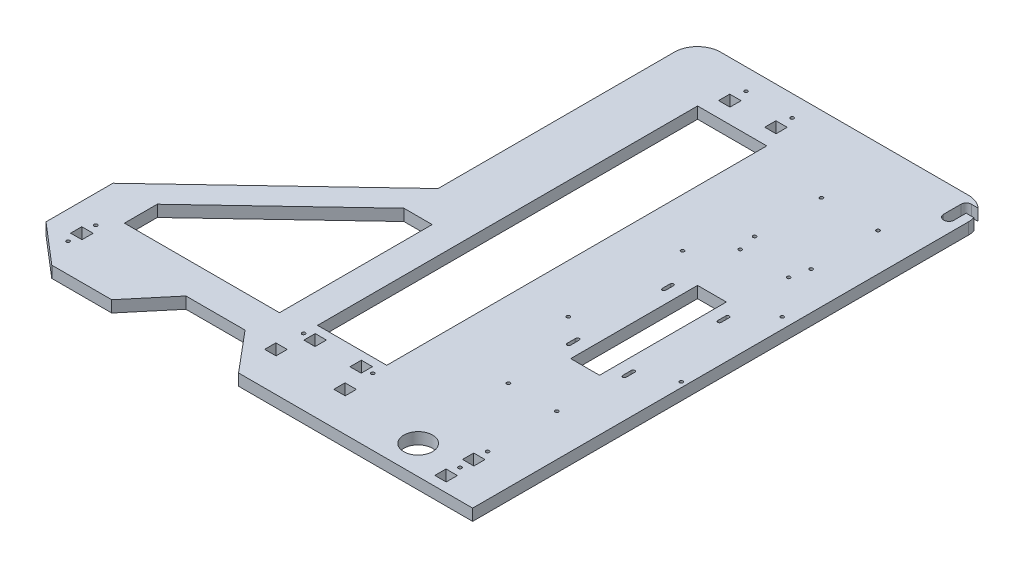
SolidWorks part; units mm, degrees
ref_plane "Front Plane" through (0, 0, 0) normal (0, 0, 1) x (1, 0, 0)
ref_plane "Top Plane" through (0, 0, 0) normal (0, 1, 0) x (1, 0, 0)
ref_plane "Right Plane" through (0, 0, 0) normal (1, 0, 0) x (0, 0, -1)
sketch "Sketch1" plane through (0, 0, 0) normal (0, 1, 0) x (1, 0, 0)
  line L0 (0, 0) -> (-235, 0)
  line L1 (-235, 0) -> (-235, -225)
  line L2 (-235, -225) -> (-380, -362)
  line L3 (-380, -362) -> (-380, -420)
  line L4 (-380, -420) -> (-345, -450)
  line L5 (-345, -450) -> (-293, -450)
  line L6 (-293, -450) -> (-263.6315, -415)
  line L7 (-263.6315, -415) -> (-212.3685, -415)
  line L8 (-212.3685, -415) -> (-183, -450)
  line L9 (-183, -450) -> (0, -450)
  line L10 (0, 0) -> (0, -450)
  line L12 (-293, -450) -> (-183, -450) construction
  dimension "D3" = 235
  dimension "D5" = 58
  dimension "D13" = 190
  dimension "D7" = 35
  dimension "D15" = 52
  dimension "D12" = 30
  dimension "D10" = 35
  dimension "D6" = 380
  dimension "D4" = 450
  dimension "D2" = 50
  dimension "D8" = 50
  dimension "D9" = 110
extrude "Boss-Extrude1" add sketch "Sketch1" along normal blind 10
sketch "Sketch16" plane through (0, 10, 0) normal (0, 1, 0) x (1, 0, 0)
  line L0 (0, -450) -> (20, -450)
  line L1 (20, -450) -> (20, 0)
  line L2 (20, 0) -> (0, 0)
  line L3 (0, 0) -> (0, -450)
  dimension "D1" = 20
  dimension "D2" = 90
extrude "Boss-Extrude2" add sketch "Sketch16" against normal through all
sketch "Sketch2" plane through (0, 10, 0) normal (0, 1, 0) x (1, 0, 0)
  line L0 (-235, -225) -> (-235, -415) construction
  line L1 (-263.6315, -415) -> (-212.3685, -415) construction
  line L2 (-345, -450) -> (-345, -328.931) construction
  line L3 (-235, -225) -> (-380, -362) construction
  line L4 (-345, -358.5097) -> (-235, -254.5787)
  line L5 (-235, -254.5787) -> (-210.5, -254.5787)
  line L6 (-210.5, -254.5787) -> (-210.5, -387)
  line L7 (-210.5, -387) -> (-345, -387)
  line L8 (-345, -387) -> (-345, -358.5097)
  line L9 (0, -450) -> (0, 0) construction
  line L10 (-184.5, -380) -> (-124.5, -380)
  line L11 (-184.5, -380) -> (-184.5, -50.425)
  line L12 (-184.5, -50.425) -> (-124.5, -50.425)
  line L13 (-124.5, -380) -> (-124.5, -50.425)
  line L14 (-124.5, -392.1) -> (-184.5, -392.1) construction
  line L15 (-16, -450) -> (-16, 0) construction
  line L16 (20, 0) -> (-235, 0) construction
  line L17 (-355.9, -440.6571) -> (-355.9, -339.2297) construction
  line L18 (-20.925, -441.85) -> (-11.075, -441.85)
  line L19 (-20.925, -441.85) -> (-20.925, -432.15)
  line L20 (-20.925, -432.15) -> (-11.075, -432.15)
  line L21 (-11.075, -441.85) -> (-11.075, -432.15)
  line L22 (-20.925, -441.85) -> (-11.075, -432.15) construction
  line L23 (-20.925, -432.15) -> (-11.075, -441.85) construction
  line L24 (-20.925, -417.85) -> (-11.075, -417.85)
  line L25 (-20.925, -417.85) -> (-20.925, -408.15)
  line L26 (-20.925, -408.15) -> (-11.075, -408.15)
  line L27 (-11.075, -417.85) -> (-11.075, -408.15)
  line L28 (-20.925, -417.85) -> (-11.075, -408.15) construction
  line L29 (-20.925, -408.15) -> (-11.075, -417.85) construction
  line L30 (-380, -420) -> (-345, -450) construction
  line L32 (-350.975, -408.15) -> (-360.825, -408.15)
  line L33 (-350.975, -408.15) -> (-350.975, -417.85)
  line L34 (-350.975, -417.85) -> (-360.825, -417.85)
  line L35 (-360.825, -408.15) -> (-360.825, -417.85)
  line L36 (-350.975, -408.15) -> (-360.825, -417.85) construction
  line L37 (-350.975, -417.85) -> (-360.825, -408.15) construction
  line L38 (-183, -450) -> (20, -450) construction
  line L39 (-183, -450) -> (20, -450) construction
  line L40 (-173.749, -32.425) -> (-113.749, -32.425) construction
  line L41 (-154.5, -50.425) -> (-154.5, -32.425) construction
  line L42 (-179.425, -27.575) -> (-169.575, -27.575)
  line L43 (-179.425, -27.575) -> (-179.425, -37.275)
  line L44 (-179.425, -37.275) -> (-169.575, -37.275)
  line L45 (-169.575, -27.575) -> (-169.575, -37.275)
  line L46 (-179.425, -27.575) -> (-169.575, -37.275) construction
  line L47 (-179.425, -37.275) -> (-169.575, -27.575) construction
  line L48 (-129.575, -37.275) -> (-139.425, -27.575) construction
  line L49 (-129.575, -27.575) -> (-139.425, -37.275) construction
  line L50 (-139.425, -27.575) -> (-139.425, -37.275)
  line L51 (-129.575, -37.275) -> (-139.425, -37.275)
  line L52 (-129.575, -27.575) -> (-129.575, -37.275)
  line L53 (-129.575, -27.575) -> (-139.425, -27.575)
  line L54 (-174.5, -32.425) -> (-174.5, -18.425) construction
  line L55 (-134.5, -32.425) -> (-134.5, -18.425) construction
  line L56 (-154.5, -380) -> (-154.5, -450) construction
  line L57 (-174.5, -392.1) -> (-134.5, -392.1) construction
  line L58 (-129.65, -397.025) -> (-139.35, -387.175) construction
  line L59 (-179.35, -387.175) -> (-169.65, -387.175)
  line L60 (-179.35, -387.175) -> (-179.35, -397.025)
  line L61 (-179.35, -397.025) -> (-169.65, -397.025)
  line L62 (-169.65, -387.175) -> (-169.65, -397.025)
  line L63 (-179.35, -387.175) -> (-169.65, -397.025) construction
  line L64 (-179.35, -397.025) -> (-169.65, -387.175) construction
  line L65 (-129.65, -387.175) -> (-139.35, -397.025) construction
  line L66 (-139.35, -387.175) -> (-139.35, -397.025)
  line L67 (-129.65, -397.025) -> (-139.35, -397.025)
  line L68 (-129.65, -387.175) -> (-129.65, -397.025)
  line L69 (-129.65, -387.175) -> (-139.35, -387.175)
  line L70 (-119.575, -420.95) -> (-129.425, -411.25) construction
  line L71 (-189.425, -411.25) -> (-179.575, -411.25)
  line L72 (-189.425, -411.25) -> (-189.425, -420.95)
  line L73 (-189.425, -420.95) -> (-179.575, -420.95)
  line L74 (-179.575, -411.25) -> (-179.575, -420.95)
  line L75 (-189.425, -411.25) -> (-179.575, -420.95) construction
  line L76 (-189.425, -420.95) -> (-179.575, -411.25) construction
  line L77 (-119.575, -411.25) -> (-129.425, -420.95) construction
  line L78 (-129.425, -411.25) -> (-129.425, -420.95)
  line L79 (-119.575, -420.95) -> (-129.425, -420.95)
  line L80 (-119.575, -411.25) -> (-119.575, -420.95)
  line L81 (-119.575, -411.25) -> (-129.425, -411.25)
  line L82 (-360.825, -408.15) -> (-11.075, -408.15) construction
  circle A0 centre (-16, -425) radius 1.45
  circle A1 centre (-16, -401) radius 1.45
  circle A2 centre (-355.9, -425) radius 1.45
  circle A3 centre (-355.9, -401) radius 1.45
  circle A4 centre (-174.5, -18.425) radius 1.45
  circle A5 centre (-134.5, -18.425) radius 1.45
  circle A6 centre (-124.5, -392.1) radius 1.45
  circle A7 centre (-184.5, -392.1) radius 1.45
  point P25 (-16, -437)
  point P30 (-16, -413)
  point P44 (-355.9, -413)
  point P61 (-174.5, -32.425)
  point P72 (-134.5, -32.425)
  point P85 (-174.5, -392.1)
  point P94 (-134.5, -392.1)
  point P95 (-184.5, -416.1)
  point P104 (-124.5, -416.1)
  point P105 (-154.5, -392.1)
  dimension "D13" = 2.9
  dimension "D14" = 2.9
  dimension "D23" = 2.9
  dimension "D24" = 2.9
  dimension "D31" = 2.9
  dimension "D37" = 2.9
  dimension "D1" = 21.5
  dimension "D2" = 28
  dimension "D3" = 24.5
  dimension "D4" = 60
  dimension "D7" = 26
  dimension "D8" = 9.7
  dimension "D9" = 9.85
  dimension "D10" = 9.85
  dimension "D11" = 9.7
  dimension "D12" = 24
  dimension "D15" = 24
  dimension "D19" = 9.85
  dimension "D20" = 9.7
  dimension "D26" = 12
  dimension "D27" = 9.85
  dimension "D28" = 9.7
  dimension "D33" = 9.7
  dimension "D38" = 9.85
  dimension "D39" = 9.7
  dimension "D41" = 24
  dimension "D34" = 30
  dimension "D36" = 12.1
  dimension "D30" = 18
  dimension "D29" = 40
  dimension "D17" = 13
  dimension "D32" = 14
  dimension "D35" = 20
  dimension "D16" = 12
  dimension "D21" = 90
  dimension "D25" = 24
  dimension "D5" = 359.75
  dimension "D22" = 349.75
  dimension "D40" = 30
  dimension "D6" = 70
  dimension "D42" = 0
  dimension "D43" = 0
  dimension "D18" = 16
  dimension "D44" = 9.85
extrude "Cut-Extrude1" cut sketch "Sketch2" against normal through all
fillet "Fillet1" radius 20 2 edges at (-235, 5, 0) (20, 5, 0)
sketch "Sketch11" plane through (0, 10, 0) normal (0, 1, 0) x (1, 0, 0)
  line L0 (-124.5, -215.2125) -> (20, -215.2125) construction
  line L1 (20, -450) -> (20, -20) construction
  line L3 (-52.25, -215.2125) -> (-52.25, -450) construction
  line L6 (-124.5, -380) -> (-124.5, -50.425) construction
  line L8 (-183, -450) -> (20, -450) construction
  circle A0 centre (-52.25, -425) radius 12.5
  circle A1 centre (-16, -425) radius 1.45 construction
  dimension "D1" = 25
  dimension "D2" = 0
  dimension "D3" = 0
extrude "WiringHole" cut sketch "Sketch11" against normal through all
sketch "Sketch9" [suppressed] plane through (0, 10, 0) normal (0, 1, 0) x (1, 0, 0)
  line L0 (-52.25, -402.5) -> (-52.25, 0) construction
  line L1 (0, 0) -> (-215, 0) construction
  line L2 (-124.5, -205.225) -> (20, -205.225) construction
  line L3 (-124.5, -365) -> (-124.5, -45.45) construction
  line L4 (-4.75, -116.725) -> (-4.75, -293.725) construction
  line L6 (-99.75, -116.725) -> (-4.75, -116.725) construction
  line L7 (-4.75, -293.725) -> (-99.75, -293.725) construction
  line L8 (-99.75, -293.725) -> (-99.75, -116.725) construction
  line L9 (20, -440) -> (20, -20) construction
  circle A0 centre (-52.25, -415) radius 12.5 construction
  circle A1 centre (-99.75, -116.725) radius 1.45
  circle A2 centre (-4.75, -116.725) radius 1.45
  circle A3 centre (-4.75, -293.725) radius 1.45
  circle A4 centre (-99.75, -293.725) radius 1.45
  dimension "D3" = 2.9
  dimension "D4" = 2.9
  dimension "D1" = 95
  dimension "D2" = 177
  dimension "D5" = 47.5
extrude "MountingHoles-PSU" [suppressed] cut sketch "Sketch9" against normal through all
sketch "Sketch10" plane through (0, 10, 0) normal (0, 1, 0) x (1, 0, 0)
  line L0 (-124.5, -215.2125) -> (20, -215.2125) construction
  line L1 (20, -450) -> (20, -20) construction
  line L2 (-49.75, -240.2125) -> (-24.75, -240.2125) construction
  line L3 (-37.25, -210.225) -> (-37.25, 0) construction
  line L4 (-52.25, -215.2125) -> (-52.25, -184.5972) construction
  line L7 (-124.5, -380) -> (-124.5, -50.425) construction
  line L8 (-49.75, -295.2125) -> (-24.75, -295.2125)
  line L9 (-49.75, -295.2125) -> (-49.75, -185.2125)
  line L10 (-49.75, -185.2125) -> (-24.75, -185.2125)
  line L11 (-24.75, -295.2125) -> (-24.75, -185.2125)
  line L12 (-49.75, -295.2125) -> (-24.75, -185.2125) construction
  line L13 (-49.75, -185.2125) -> (-24.75, -295.2125) construction
  line L15 (0, 0) -> (-215, 0) construction
  line L17 (-37.25, -210.225) -> (-37.25, -450) construction
  line L18 (-183, -450) -> (20, -450) construction
  line L19 (-64.75, -215.2125) -> (-39.75, -215.2125) construction
  line L20 (-37.25, -295.2125) -> (-37.25, -185.2125) construction
  dimension "D1" = 25
  dimension "D2" = 110
  dimension "D3" = 0
  dimension "D4" = 0
  dimension "D5" = 0
  dimension "D6" = 25
  dimension "D7" = 15
extrude "WiringSlot" cut sketch "Sketch10" against normal through all
sketch "CenterLines" plane through (0, 10, 0) normal (0, 1, 0) x (1, 0, 0)
  line L0 (-37.25, -295.2125) -> (-37.25, -185.2125) construction
  line L1 (-49.75, -295.2125) -> (-24.75, -295.2125) construction
  line L2 (-24.75, -185.2125) -> (-49.75, -185.2125) construction
  line L3 (-49.75, -240.2125) -> (-24.75, -240.2125) construction
  line L4 (-49.75, -185.2125) -> (-49.75, -295.2125) construction
  line L5 (-24.75, -295.2125) -> (-24.75, -185.2125) construction
ref_plane "Plane1" through (-37.25, 0, 0) normal (1, 0, 0) x (0, 0, -1)
sketch "Sketch6" plane through (0, 10, 0) normal (0, 1, 0) x (1, 0, 0)
  line L0 (-37.25, -295.2125) -> (-37.25, -185.2125) construction
  line L1 (-61.35, -240.2125) -> (-13.15, -240.2125) construction
  line L2 (-13.15, -195.7625) -> (-13.15, -278.2625) construction
  line L3 (-49.75, -295.2125) -> (-24.75, -295.2125) construction
  line L4 (-49.75, -240.2125) -> (-24.75, -240.2125) construction
  line L5 (-24.75, -185.2125) -> (-49.75, -185.2125) construction
  line L6 (-13.15, -195.7625) -> (-13.15, -202.7625) construction
  line L7 (-11.7, -195.7625) -> (-11.7, -202.7625)
  line L8 (-14.6, -195.7625) -> (-14.6, -202.7625)
  line L9 (-49.75, -240.2125) -> (-24.75, -240.2125) construction
  line L10 (-49.75, -185.2125) -> (-49.75, -295.2125) construction
  line L11 (-24.75, -295.2125) -> (-24.75, -185.2125) construction
  line L12 (-13.15, -285.2625) -> (-13.15, -278.2625) construction
  line L13 (-14.6, -285.2625) -> (-14.6, -278.2625)
  line L14 (-61.35, -277.6625) -> (-61.35, -202.7625) construction
  line L15 (-13.15, -285.2625) -> (-13.15, -202.7625) construction
  line L16 (-11.7, -285.2625) -> (-11.7, -278.2625)
  arc A2 (-11.7, -195.7625) -> (-14.6, -195.7625) centre (-13.15, -195.7625) ccw
  arc A3 (-14.6, -202.7625) -> (-11.7, -202.7625) centre (-13.15, -202.7625) ccw
  circle A4 centre (-61.35, -277.6625) radius 1.45
  circle A6 centre (-61.35, -202.7625) radius 1.45
  arc A8 (-14.6, -285.2625) -> (-11.7, -285.2625) centre (-13.15, -285.2625) ccw
  arc A9 (-11.7, -278.2625) -> (-14.6, -278.2625) centre (-13.15, -278.2625) ccw
  point P20 (-13.15, -199.2625)
  point P25 (-13.15, -281.7625)
  dimension "D6" = 0
  dimension "D8" = 2.9
  dimension "D12" = 2.9
  dimension "D4" = 1.45
  dimension "D5" = 1.45
  dimension "D11" = 82.5
  dimension "D14" = 74.9
  dimension "D2" = 24.1
  dimension "D3" = 48.2
  dimension "D9" = 7
  dimension "D10" = 7
extrude "MountingHoles-RAMPS" cut sketch "Sketch6" against normal through all
mirror "Mirror1" about plane through (-37.25, 0, 0) normal (1, 0, 0) of "MountingHoles-RAMPS"
sketch "Sketch5" plane through (0, 10, 0) normal (0, 1, 0) x (1, 0, 0)
  line L0 (-24.75, -240.2125) -> (-49.75, -240.2125) construction
  line L3 (-24.75, -295.2125) -> (-24.75, -185.2125) construction
  line L5 (-49.75, -185.2125) -> (-49.75, -295.2125) construction
  line L7 (-16.25, -139.7125) -> (-58.25, -139.7125) construction
  line L8 (-16.25, -340.7125) -> (-58.25, -340.7125) construction
  line L9 (-37.25, -240.2125) -> (-37.25, -139.7125) construction
  line L10 (-37.25, -240.2125) -> (-37.25, -340.7125) construction
  circle A0 centre (-58.25, -139.7125) radius 1.45
  circle A1 centre (-16.25, -139.7125) radius 1.45
  circle A2 centre (-16.25, -340.7125) radius 1.45
  circle A3 centre (-58.25, -340.7125) radius 1.45
  point P17 (-37.25, -139.7125)
  point P22 (-37.25, -340.7125)
  dimension "D2" = 2.9
  dimension "D5" = 2.9
  dimension "D6" = 2.9
  dimension "D7" = 2.9
  dimension "D3" = 201
  dimension "D4" = 100.5
  dimension "D8" = 21
  dimension "D9" = 21
  dimension "D10" = 100.5
extrude "MountingHoles-Melzi" cut sketch "Sketch5" against normal through all
sketch "Sketch13" plane through (0, 0, 0) normal (0, -1, 0) x (-1, 0, 0)
  line L0 (49.75, -215.2125) -> (124.5, -215.2125) construction
  line L1 (124.5, -380) -> (124.5, -50.425) construction
  line L2 (82.25, -264.7275) -> (82.25, -165.6975) construction
  line L3 (37.25, -295.2125) -> (37.25, -185.2125) construction
  line L4 (49.75, -185.2125) -> (49.75, -295.2125) construction
  line L6 (82.25, -264.7275) -> (-15.65, -264.7275) construction
  circle A0 centre (82.25, -165.6975) radius 1.45
  circle A1 centre (82.25, -264.7275) radius 1.45
  circle A2 centre (-10.59, -172.1775) radius 1.45
  circle A3 centre (-15.65, -264.7275) radius 1.45
  point P11 (82.25, -215.2125)
  dimension "D8" = 2.9
  dimension "D6" = 2.9
  dimension "D1" = 2.9
  dimension "D2" = 49.515
  dimension "D3" = 45
  dimension "D4" = 6.48
  dimension "D5" = 92.84
  dimension "D7" = 97.9
extrude "Mountingholes-Smoothieboard" cut sketch "Sketch13" against normal through all
mirror "Flipped" [suppressed] about plane through (-37.25, 0, 0) normal (1, 0, 0)
sketch "Sketch21" plane through (0, 10, 0) normal (0, 1, 0) x (1, 0, 0)
  line L0 (-37.25, -185.2125) -> (-37.25, 0) construction
  line L1 (-24.75, -185.2125) -> (-49.75, -185.2125) construction
  line L2 (0, 0) -> (-215, 0) construction
  line L3 (-37.25, -94.7125) -> (-23.3697, -94.7125) construction
  circle A0 centre (-12.75, -65.7125) radius 1.45
  circle A1 centre (-61.75, -65.7125) radius 1.45
  circle A2 centre (-61.75, -123.7125) radius 1.45
  circle A3 centre (-12.75, -123.7125) radius 1.45
  circle A4 centre (-16.25, -139.7125) radius 1.45 construction
  dimension "D1" = 2.9
  dimension "D2" = 24.5
  dimension "D3" = 29
  dimension "D4" = 45
extrude "Pi" cut sketch "Sketch21" against normal through all
sketch "Sketch17" plane through (0, 10, 0) normal (0, 1, 0) x (1, 0, 0)
  line L0 (0, 0) -> (20, 0) construction
  line L1 (20, -23.6361) -> (20, 0) construction
  line L2 (20, -450) -> (20, -20) construction
  line L3 (20, -10) -> (8, -10) construction
  line L4 (20, -14.5) -> (8, -14.5)
  line L5 (20, -5.5) -> (8, -5.5)
  arc A0 (20, -14.5) -> (20, -5.5) centre (20, -10) ccw
  arc A1 (8, -5.5) -> (8, -14.5) centre (8, -10) ccw
  point P8 (14, -10)
  dimension "D1" = 9
  dimension "D2" = 12
  dimension "D3" = 10
extrude "Cut-Extrude3" cut sketch "Sketch17" against normal through all
sketch "Sketch18" plane through (0, 10, 0) normal (0, 1, 0) x (1, 0, 0)
  line L0 (8, -5.5) -> (8, -14.5) construction
  line L1 (3.5, -10) -> (8, -10) construction
  line L2 (8, -10) -> (8, -25) construction
  line L3 (12.5, -10) -> (12.5, -25)
  line L4 (3.5, -10) -> (3.5, -25)
  arc A0 (8, -5.5) -> (8, -14.5) centre (8, -10) ccw construction
  arc A1 (12.5, -10) -> (3.5, -10) centre (8, -10) ccw
  arc A2 (3.5, -25) -> (12.5, -25) centre (8, -25) ccw
  point P10 (8, -17.5)
  dimension "D1" = 9
  dimension "D2" = 0
  dimension "D3" = 15
extrude "Cut-Extrude4" cut sketch "Sketch18" against normal through all
sketch "Sketch19" plane through (0, 10, 0) normal (0, 1, 0) x (1, 0, 0)
  line L0 (-2, -25) -> (18, -25) construction
  line L1 (8, -25) -> (8, -5.5) construction
  circle A0 centre (18, -25) radius 1.45
  arc A1 (8, -5.5) -> (3.5, -10) centre (8, -10) ccw construction
  circle A2 centre (-2, -25) radius 1.45
  dimension "D2" = 2.9
extrude "Cut-Extrude5" [suppressed] cut sketch "Sketch19" against normal through all
equation "\"Y-ROD-SPACING\"=75"
equation "\"Y-BED-OFFSET\"=2"
equation "\"Y-BED-ROD-INSET\"=3.5"
equation "\"T-SLOT-NUT-FILLET-RADIUS\"=0.5"
equation "\"T-SLOT-SCREW-SHAFT-RADIUS\"=1.55"
equation "\"T-SLOT-SCREW-SHAFT-CUTOUT-LENGTH\"=11"
equation "\"T-SLOT-NUT-DEPTH\"=3.5"
equation "\"T-SLOT-NUT-WIDTH\"=2.85"
equation "\"T-SLOT-NUT-END-DISTANCE\"=8"
equation "\"ACRYLIC-TAB-CUTOUT-SIZE\"=\"ACRYLIC-THICKNESS\"+\"ACRYLIC-TAB-TOLERANCE\"*2"
equation "\"ACRYLIC-TAB-WIDTH\"=\"ACRYLIC-THICKNESS\""
equation "\"ACRYLIC-M3-HOLE\"=2.9"
equation "\"SMOOTHROD-CAP-SCREW-DISTANCE\"=20"
equation "\"FRAME-WIDTH-INNER\"=370"
equation "\"D24@Sketch2\"=\"ACRYLIC-M3-HOLE\""
equation "\"D23@Sketch2\"=\"ACRYLIC-M3-HOLE\""
equation "\"D19@Sketch2\"=\"ACRYLIC-THICKNESS\"-\"KERF\"*2"
equation "\"D20@Sketch2\"=\"ACRYLIC-TAB-WIDTH\"-\"KERF\"*4"
equation "\"D37@Sketch2\"=\"ACRYLIC-M3-HOLE\""
equation "\"D33@Sketch2\"=\"ACRYLIC-TAB-WIDTH\"-\"KERF\"*4"
equation "\"D38@Sketch2\"=\"ACRYLIC-THICKNESS\"-\"KERF\"*2"
equation "\"D39@Sketch2\"=\"ACRYLIC-TAB-WIDTH\"-\"KERF\"*4"
equation "\"D13@Sketch2\"=\"ACRYLIC-M3-HOLE\""
equation "\"D14@Sketch2\"=\"ACRYLIC-M3-HOLE\""
equation "\"D8@Sketch2\"=\"ACRYLIC-TAB-WIDTH\"-\"KERF\"*4"
equation "\"D9@Sketch2\"=\"ACRYLIC-THICKNESS\"-\"KERF\"*2"
equation "\"D10@Sketch2\"=\"ACRYLIC-THICKNESS\"-\"KERF\"*2"
equation "\"D11@Sketch2\"=\"ACRYLIC-TAB-WIDTH\"-\"KERF\"*4"
equation "\"D31@Sketch2\"=\"ACRYLIC-M3-HOLE\""
equation "\"D27@Sketch2\"=\"ACRYLIC-THICKNESS\"-\"KERF\"*2"
equation "\"D28@Sketch2\"=\"ACRYLIC-TAB-WIDTH\"-\"KERF\"*4"
equation "\"NEMA17-HOLE-SPACING\"=31"
equation "\"NEMA17-CENTRAL-CUTOUT\"=22.5"
equation "\"Z-BRACKET-REACH\"=57"
equation "\"TOP-BRACKET-SPACING\"=40"
equation "\"D29@Sketch2\"=\"TOP-BRACKET-SPACING\""
equation "\"ACRYLIC-THICKNESS\"=10"
equation "\"SMOOTHROD-Z-LENGTH\"=350"
equation "\"D5@Sketch2\"=\"SMOOTHROD-Z-LENGTH\"-\"SMOOTHROD-TIGHTENING-HEADROOM\"+10"
equation "\"SMOOTHROD-X-LENGTH\"=350"
equation "\"SMOOTHROD-Y-LENGTH\"=350"
equation "\"D22@Sketch2\"=\"SMOOTHROD-Y-LENGTH\"-\"SMOOTHROD-TIGHTENING-HEADROOM\""
equation "\"SMOOTHROD-TIGHTENING-HEADROOM\"=.25"
equation "\"X-ROD-SPACING\"=45"
equation "\"Z-ROD-SPACING\"=17.5"
equation "\"LEADSCREW-Z-LENGTH\"=300"
equation "\"SCREW-HEAD-RADIUS\"=6"
equation "\"PRINTED-X-SMOOTHROD-DIAMETER\"=8.8"
equation "\"PRINTED-X-SMOOTHROD-CUTOUT\"=10"
equation "\"PRINTED-X-BASE-HEIGHT\"=10"
equation "\"PRINTED-LM8UU-CUTOUT-SIZE\"=15.5"
equation "\"PRINTED-LM8UU-CUTOUT-LENGTH\"=24.5"
equation "\"PRINTED-X-IDLER-HEIGHT\"=16"
equation "\"PSU-MOUNTING-WIDTH\"=95"
equation "\"PSU-MOUNTING-HEIGHT\"=177"
equation "\"D1@Sketch9\"=\"PSU-MOUNTING-WIDTH\""
equation "\"D3@Sketch9\"=\"ACRYLIC-M3-HOLE\""
equation "\"D1@Boss-Extrude1\"=\"ACRYLIC-THICKNESS\""
equation "\"D6@Sketch1\"=\"SMOOTHROD-Y-LENGTH\"+30"
equation "\"D4@Sketch9\"=\"ACRYLIC-M3-HOLE\""
equation "\"D2@Sketch9\"=\"PSU-MOUNTING-HEIGHT\""
equation "\"D5@Sketch9\"=\"PSU-MOUNTING-WIDTH\"/2"
equation "\"D4@Sketch1\"=\"SMOOTHROD-Z-LENGTH\"+100"
equation "\"D8@Sketch6\"=\"ACRYLIC-M3-HOLE\""
equation "\"D12@Sketch6\"=\"ACRYLIC-M3-HOLE\""
equation "\"D2@Sketch5\"=\"ACRYLIC-M3-HOLE\""
equation "\"D5@Sketch5\"=\"ACRYLIC-M3-HOLE\""
equation "\"D6@Sketch5\"=\"ACRYLIC-M3-HOLE\""
equation "\"D7@Sketch5\"=\"ACRYLIC-M3-HOLE\""
equation "\"D1@Sketch13\"=\"ACRYLIC-M3-HOLE\""
equation "\"D6@Sketch13\"=\"ACRYLIC-M3-HOLE\""
equation "\"D8@Sketch13\"=\"ACRYLIC-M3-HOLE\""
equation "\"D4@Sketch6\"=\"ACRYLIC-M3-HOLE\"/2"
equation "\"D5@Sketch6\"=\"ACRYLIC-M3-HOLE\"/2"
equation "\"Y-BED-SCREW-SPACING\"=209"
equation "\"Y-BED-SCREW-CUTOUT-SLOT-HEIGHT\"=2"
equation "\"ACRYLIC-THICKNESS2\"=4.5"
equation "\"ACRYLIC-TAB-TOLERANCE\"=-.05"
equation "\"Z-ROD-INSET\"=13.5"
equation "\"SCREW-LENGTH-FRAME\"=\"ACRYLIC-THICKNESS\" + 10"
equation "\"SCREW-LENGTH-MOTOR\"=\"ACRYLIC-THICKNESS\" + 5"
equation "\"SCREW-LENGTH-EXTRUDER\"=28"
equation "\"Y-BELT-TO-ROD-DISTANCE\"=20"
equation "\"SPOOL-HOLDER-ROD-SPACING\"=150"
equation "\"ACRYLIC-X-CARRIAGE-WIDTH\"=55"
equation "\"ACRYLIC-X-CARRIAGE-HEIGHT\"=75"
equation "\"ACRYLIC-X-CARRIAGE-LM8UU-CUTOUT-WIDTH\"=24.25"
equation "\"ACRYLIC-X-CARRIAGE-SCREW-SPACING-X\"=15"
equation "\"ACRYLIC-X-CARRIAGE-SCREW-SPACING-Y\"=33"
equation "\"ACRYLIC-X-CARRIAGE-CENTER-TAB-SPACING\"=14"
equation "\"ACRYLIC-X-CARRIAGE-EXTRUDER-OFFSET\"=26"
equation "\"ACRYLIC-X-CARRIAGE-EXTRUDER-ANGLE\"=90"
equation "\"ACRYLIC-X-CARRIAGE-EXTRUDER-SHELF-DEPTH\"=\"ACRYLIC-X-CARRIAGE-EXTRUDER-OFFSET\" + 28"
equation "\"ACRYLIC-X-CARRIAGE-EXTRUDER-BRACE-SPACING\"=23"
equation "\"ACRYLIC-X-CARRIAGE-EXTRUDER-BRACE-TAB-OFFSET\"=20"
equation "\"ACRYLIC-X-CARRIAGE-EXTRUDER-BRACE-HEIGHT\"=35"
equation "\"ACRYLIC-X-CARRIAGE-EXTRUDER-BRACE-SCREW-SPACING\"=22"
equation "\"D1@Sketch19\"=\"SMOOTHROD-CAP-SCREW-DISTANCE\"/2"
equation "\"D2@Sketch19\"=\"ACRYLIC-M3-HOLE\""
equation "\"D1@Sketch21\"=\"ACRYLIC-M3-HOLE\""
equation "\"KERF\"=0.075"
equation "\"PRINTED-M3-HOLE\"=3.5"
equation "\"PRINTED-M3-NUT-AF\"=6.25"
equation "\"ACRYLIC-X-CARRIAGE-LM8UU-CUTOUT-HEIGHT\"=11.0"
equation "\"ACRYLIC-X-CARRIAGE-DUAL-WIDTH-MULTIPLIER\"=1.65"
equation "\"ACRYLIC-X-CARRIAGE-DUAL-HOTEND-SPACING\"=42"
equation "\"ACRYLIC-X-CARRIAGE-DUAL-WIDTH\"=75"
equation "\"ACRYLIC-X-CARRIAGE-DUAL-FAN-OFFSET\"=52"
equation "\"ACRYLIC-X-CARRIAGE-DUAL-FAN-HEIGHT\"=20"
equation "\"ACRYLIC-X-CARRIAGE-DUAL-HOTEND-SEPARATION\"=36"
equation "\"ACRYLIC-X-CARRIAGE-DUAL-MOUNT-PLATE-DEPTH\"=75"
equation "\"ACRYLIC-X-CARRIAGE-DUAL-MOUNT-BRACE-WIDTH\"=33"
equation "\"ACRYLIC-X-CARRIAGE-DUAL-MOUNT-SCREW-WIDTH\"=40"
equation "\"BLOWER-FAN-WIDTH\"=15"
equation "\"D44@Sketch2\"=\"ACRYLIC-THICKNESS\"-\"KERF\"*2"
